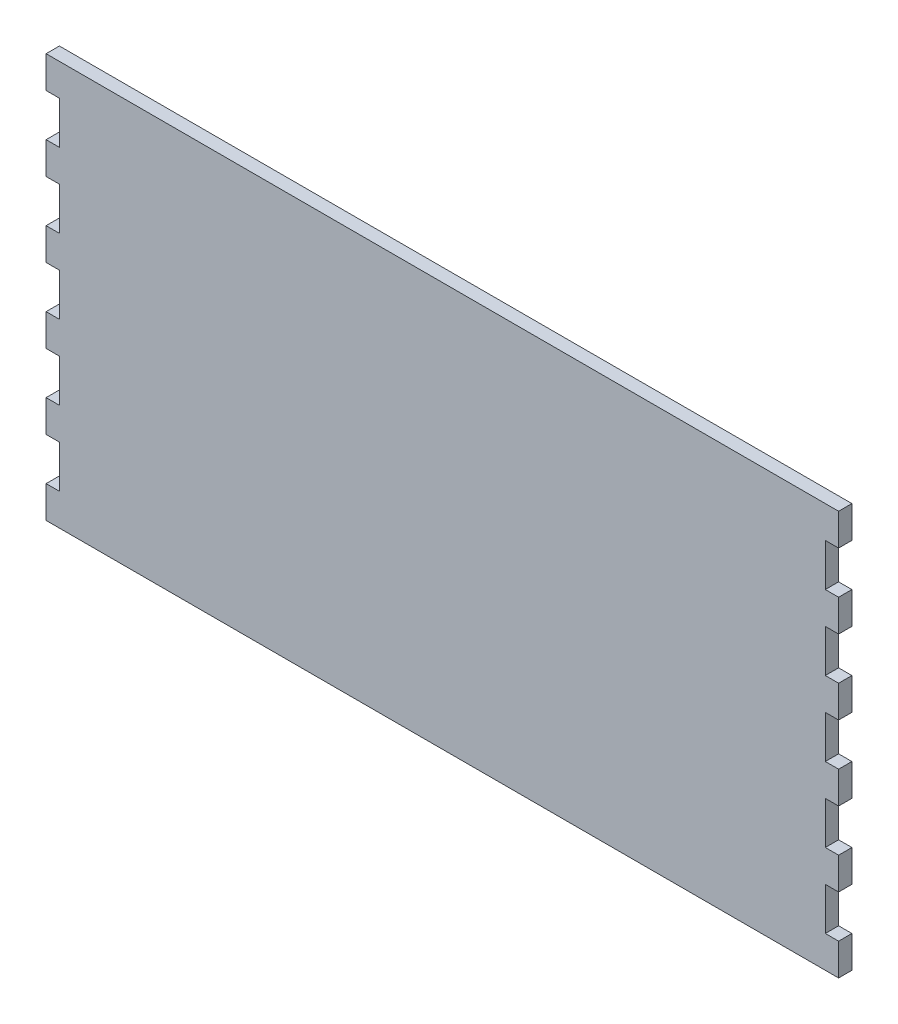
SolidWorks part; units mm, degrees
ref_plane "Front Plane" through (0, 0, 0) normal (0, 0, 1) x (1, 0, 0)
ref_plane "Top Plane" through (0, 0, 0) normal (0, 1, 0) x (1, 0, 0)
ref_plane "Right Plane" through (0, 0, 0) normal (1, 0, 0) x (0, 0, -1)
sketch "Sketch1" plane through (0, 0, 0) normal (0, 0, 1) x (1, 0, 0)
  line L1 (-83.4402, 47.9217) -> (105.7898, 47.9217)
  line L2 (-83.4402, 47.9217) -> (-83.4402, -48.5983)
  line L3 (-83.4402, -48.5983) -> (105.7898, -48.5983)
  line L4 (105.7898, 47.9217) -> (105.7898, -48.5983)
  dimension "D1" = 96.52
  dimension "D2" = 189.23
extrude "Boss-Extrude1" add sketch "Sketch1" along normal blind 3.175
sketch "Sketch2" plane through (0, 0, 3.175) normal (0, 0, 1) x (1, 0, 0)
  line L0 (-83.4402, 47.9217) -> (-83.4402, -48.5983) construction
  line L1 (-83.4402, 40.3017) -> (-80.2652, 40.3017)
  line L2 (-83.4402, 40.3017) -> (-83.4402, 30.1417)
  line L3 (-83.4402, 30.1417) -> (-80.2652, 30.1417)
  line L4 (-80.2652, 40.3017) -> (-80.2652, 30.1417)
  line L5 (-83.4402, 40.3017) -> (-83.4402, 47.9217) construction
  line L6 (-83.4402, 30.1417) -> (-83.4402, -48.5983) construction
  dimension "D1" = 3.175
  dimension "D2" = 7.62
  dimension "D3" = 10.16
extrude "Cut-Extrude1" cut sketch "Sketch2" against normal through all contours L4 L3 L2 L1
pattern_linear "LPattern1" count 5 spacing 17.78 along (0, -1, 0) of "Cut-Extrude1"
ref_plane "Plane1" through (11.1748, 0, 0) normal (-1, 0, 0) x (0, 0, 1)
mirror "Mirror1" about plane through (11.1748, 0, 0) normal (-1, 0, 0) of "LPattern1"
